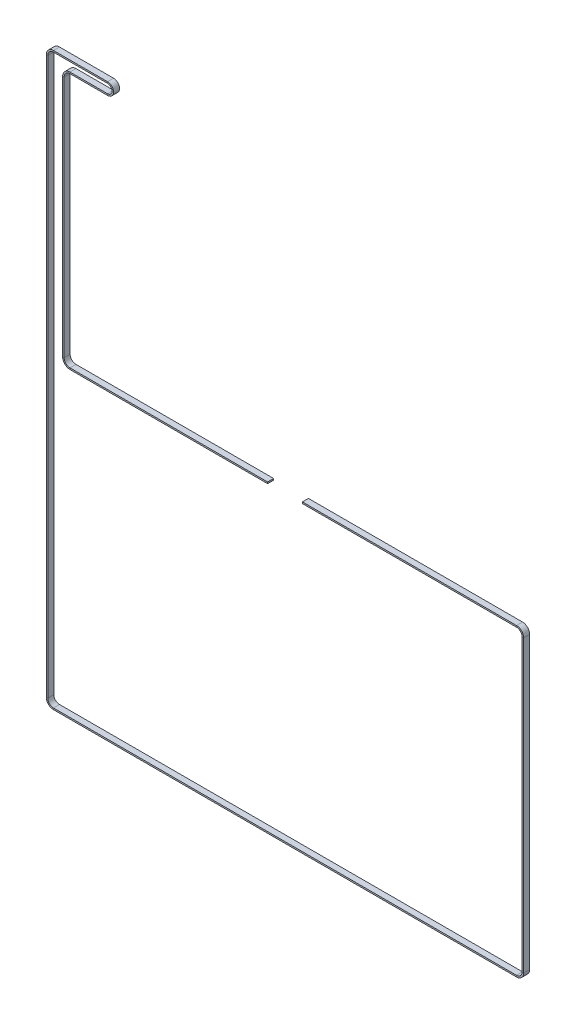
SolidWorks part; units mm, degrees
ref_plane "Front" through (0, 0, 0) normal (0, 0, 1) x (1, 0, 0)
ref_plane "Top" through (0, 0, 0) normal (0, 1, 0) x (1, 0, 0)
ref_plane "Right" through (0, 0, 0) normal (1, 0, 0) x (0, 0, -1)
sketch "Sketch1" plane through (0, -21, 4.45) normal (0, 0, 1) x (1, 0, 0)
  line L0 (10, 63.3) -> (47.5, 63.3)
  line L1 (47.5, 73.7) -> (-6.5, 73.7)
  line L2 (-12.875, 67.325) -> (-12.875, -488)
  line L3 (-6.5, -494.375) -> (455.5, -494.375)
  line L4 (461.875, -488) -> (461.875, -198.525)
  line L5 (455.5, -192.15) -> (241.85, -192.15)
  line L6 (207.15, -195.7) -> (207.15, -190.7) construction
  line L7 (3.4, 56.7) -> (3.4, -185.7)
  line L8 (10, -192.3) -> (207.15, -192.3)
  line L11 (241.85, -191.3) -> (241.85, -187.7) construction
  circle A0 centre (47.5, 68.5) radius 5.2 construction
  circle A1 centre (10, 56.7) radius 6.6 construction
  circle A2 centre (-6.5, 67.325) radius 6.375 construction
  circle A4 centre (-6.5, -488) radius 6.375 construction
  circle A5 centre (455.5, -488) radius 6.375 construction
  arc A7 (47.5, 73.7) -> (47.5, 63.3) centre (47.5, 68.5) cw
  arc A8 (10, 63.3) -> (3.4, 56.7) centre (10, 56.7) ccw
  arc A9 (-12.875, 67.325) -> (-6.5, 73.7) centre (-6.5, 67.325) cw
  arc A10 (-6.5, -494.375) -> (-12.875, -488) centre (-6.5, -488) cw
  arc A11 (455.5, -494.375) -> (461.875, -488) centre (455.5, -488) ccw
  arc A12 (461.875, -198.525) -> (455.5, -192.15) centre (455.5, -198.525) ccw
  arc A13 (3.4, -185.7) -> (10, -192.3) centre (10, -185.7) ccw
  circle A14 centre (-6.5, 67.325) radius 9 construction
  circle A15 centre (10, -185.7) radius 6.6 construction
  circle A16 centre (10, -185.7) radius 5.9875 construction
  circle A17 centre (455.5, -198.525) radius 6.375 construction
  circle A18 centre (455.5, -198.525) radius 5.9875 construction
  dimension "D1" = 12.75
ref_plane "Plane1" through (241.85, -213.15, 4.45) normal (-1, 0, 0) x (0, 0, 1)
sketch "Sketch2" plane through (241.85, -213.15, 4.45) normal (-1, 0, 0) x (0, 0, 1)
  line L1 (-3, 0.75) -> (3, 0.75)
  line L2 (-3, 0.75) -> (-3, -0.75)
  line L3 (-3, -0.75) -> (3, -0.75)
  line L4 (3, 0.75) -> (3, -0.75)
  line L5 (-3, 0.75) -> (3, -0.75) construction
  line L6 (-3, -0.75) -> (3, 0.75) construction
  point P0 (0, 0)
  dimension "D1" = 6
  dimension "D2" = 1.5
sweep "Sweep1" add profiles "Sketch2" path "Sketch1"
